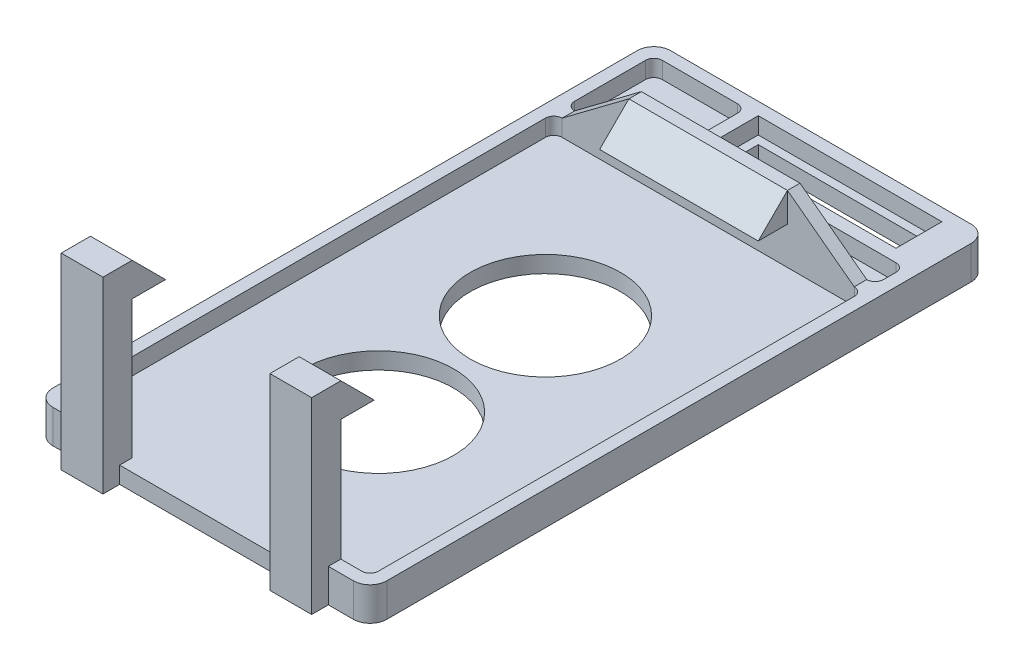
SolidWorks part; units mm, degrees
note: The reader was unsure of these and kept them because the rebuilt part matched: shared geometry of "PCB holder<52>", "PCB holder<55>", "PCB holder<57>", "PCB holder<58>", "Sketch12<3>".
ref_plane "Front Plane" through (0, 0, 0) normal (0, 0, 1) x (1, 0, 0)
ref_plane "Top Plane" through (0, 0, 0) normal (0, 1, 0) x (1, 0, 0)
ref_plane "Right Plane" through (0, 0, 0) normal (1, 0, 0) x (0, 0, -1)
sketch "PCB holder" plane through (0, 0, 0) normal (0, 1, 0) x (1, 0, 0)
  line L0 (8.75, 14.75) -> (8.75, 21.5)
  line L1 (9, 21.5) -> (-9, 21.5)
  line L2 (10, 20.5) -> (10, -14.5)
  line L3 (9, -15.5) -> (-9, -15.5)
  line L4 (-10, 20.5) -> (-10, -14.5)
  line L5 (-8.75, 14.75) -> (-8.75, 21.5)
  line L7 (8.75, 14.75) -> (-8.75, 14.75)
  line L8 (9.25, 14.25) -> (9.25, -14.25)
  line L9 (8.75, -14.75) -> (-8.75, -14.75)
  line L10 (-9.25, 14.25) -> (-9.25, -14.25)
  line L11 (-8.75, 15.5) -> (8.75, 15.5)
  line L12 (-8.75, 15.5) -> (-8.75, 14.75)
  line L13 (-4.75, 21.5) -> (4.75, 21.5)
  line L14 (-8.75, 14.75) -> (8.75, 14.75)
  line L15 (8.75, 15.5) -> (8.75, 14.75)
  line L17 (-7.5, -14.75) -> (-5, -14.75)
  line L18 (-8.75, 14.75) -> (8.75, 14.75)
  line L20 (-8.75, 21.5) -> (8.75, 21.5)
  line L22 (-7.5, -14.75) -> (-7.5, -16.5)
  line L23 (-7.5, -16.5) -> (-5, -16.5)
  line L24 (-5, -14.75) -> (-5, -16.5)
  line L25 (5, -16.5) -> (7.5, -16.5)
  line L26 (5, -16.5) -> (5, -14.75)
  line L27 (5, -14.75) -> (7.5, -14.75)
  line L28 (7.5, -16.5) -> (7.5, -14.75)
  arc A0 (-9.25, 14.25) -> (-8.75, 14.75) centre (-8.75, 14.25) cw
  arc A1 (9.25, 14.25) -> (8.75, 14.75) centre (8.75, 14.25) ccw
  arc A2 (8.75, -14.75) -> (9.25, -14.25) centre (8.75, -14.25) ccw
  arc A3 (-9.25, -14.25) -> (-8.75, -14.75) centre (-8.75, -14.25) ccw
  arc A4 (-9, 21.5) -> (-10, 20.5) centre (-9, 20.5) ccw
  arc A5 (9, 21.5) -> (10, 20.5) centre (9, 20.5) cw
  arc A6 (-10, -14.5) -> (-9, -15.5) centre (-9, -14.5) ccw
  arc A7 (10, -14.5) -> (9, -15.5) centre (9, -14.5) cw
  circle A12 centre (0, 5) radius 4.5
  circle A13 centre (0, -5) radius 4.5
  point P0 (0, 0)
  point P1 (0, 0)
  point P7 (0, 0)
  line B0 (-8.5, 14.5) -> (8.5, 14.5) construction
  line B1 (-9, 14) -> (-9, -14) construction
  line B2 (-8.5, -14.5) -> (8.5, -14.5) construction
  line B3 (9, 14) -> (9, -14) construction
  arc B4 (-9, 14) -> (-8.5, 14.5) centre (-8.5, 14) cw construction
  arc B5 (9, 14) -> (8.5, 14.5) centre (8.5, 14) ccw construction
  arc B6 (8.5, -14.5) -> (9, -14) centre (8.5, -14) ccw construction
  arc B7 (-9, -14) -> (-8.5, -14.5) centre (-8.5, -14) ccw construction
sketch_block_instance "Block2-1"
sketch_block "Block2"
extrude "Boss-Extrude1" add sketch "PCB holder" along normal blind 1 contours L10 A3 L9 A2 L8 A1 L7 A0 A13 A12 | L2 A7 L3 A6 L4 A4 L1 A5
extrude "Boss-Extrude2" add sketch "PCB holder<52>" along normal blind 1 contours L10 A3 L9 A2 L8 A1 L7 A0 A13 A12
sketch "PCB holder<52>" plane through (0, 0, 0) normal (0, 1, 0) x (1, 0, 0) same geometry as "PCB holder"
extrude "Boss-Extrude3" add sketch "PCB holder<55>" along normal blind 2 contours A7 L2 A5 L1 L0 A1 L8 A2 L9 L28 L3 | L7 L0 L1 L5 | L4 A6 L3 L22 L9 A3 L10 A0 L5 L1 A4
sketch "PCB holder<55>" plane through (0, 0, 0) normal (0, 1, 0) x (1, 0, 0) same geometry as "PCB holder"
extrude "Boss-Extrude7" add sketch "PCB holder<57>" along normal blind 5 contours L11 L5 L7 L0
sketch "PCB holder<57>" plane through (0, 0, 0) normal (0, 1, 0) x (1, 0, 0) same geometry as "PCB holder"
sketch "Sketch6" plane through (0, 0, -14.75) normal (0, 0, 1) x (1, 0, 0)
  line L1 (-4.75, 5) -> (4.75, 5)
  line L2 (-4.75, 5) -> (-4.75, 3.25)
  line L3 (-4.75, 3.25) -> (4.75, 3.25)
  line L4 (4.75, 5) -> (4.75, 3.25)
extrude "Boss-Extrude9" add sketch "Sketch6" along normal blind 1.75
sketch "Sketch7" plane through (4.75, 0, 0) normal (1, 0, 0) x (0, 0, -1)
  line L0 (13, 3.25) -> (14.75, 5)
  line L1 (14.75, 5) -> (13, 5)
  line L2 (13, 5) -> (13, 3.25)
sketch "Sketch8" plane through (0, 0, -14.75) normal (0, 0, 1) x (1, 0, 0)
  line L0 (4.75, 5) -> (8.75, 2)
  line L1 (8.75, 2) -> (8.75, 5)
  line L2 (8.75, 5) -> (4.75, 5)
  line L3 (-4.75, 5) -> (-8.75, 2)
  line L4 (-8.75, 2) -> (-8.75, 5)
  line L5 (-8.75, 5) -> (-4.75, 5)
extrude "Cut-Extrude7" cut sketch "Sketch8" against normal blind 0.75
extrude "Boss-Extrude10" add sketch "PCB holder<58>" along normal blind 11.25 contours L24 L3 L22 L23 | L24 L9 L22 L3 | L25 L28 L3 L26 | L3 L28 L9 L26
sketch "PCB holder<58>" plane through (0, 0, 0) normal (0, 1, 0) x (1, 0, 0) same geometry as "PCB holder"
sketch "Sketch10" plane through (0, 0, 14.75) normal (0, 0, -1) x (-1, 0, 0)
  line L0 (-5, 11.25) -> (-5, 1) construction
  line L1 (-7.5, 11.25) -> (-5, 11.25)
  line L2 (-7.5, 11.25) -> (-7.5, 9.25)
  line L3 (-7.5, 9.25) -> (-5, 9.25)
  line L4 (-5, 11.25) -> (-5, 9.25)
  line L5 (7.5, 11.25) -> (7.5, 2) construction
  line L6 (5, 11.25) -> (7.5, 11.25)
  line L7 (5, 11.25) -> (5, 9.25)
  line L8 (5, 9.25) -> (7.5, 9.25)
  line L9 (7.5, 11.25) -> (7.5, 9.25)
extrude "Boss-Extrude11" add sketch "Sketch10" along normal blind 2
sketch "Sketch11" plane through (7.5, 0, 0) normal (1, 0, 0) x (0, 0, -1)
  line L0 (-14.75, 11.25) -> (-12.75, 9.25)
  line L1 (-16.5, 11.25) -> (-12.75, 11.25) construction
  line L2 (-12.75, 9.25) -> (-12.75, 11.25)
  line L3 (-12.75, 11.25) -> (-12.75, 9.25) construction
  line L4 (-12.75, 11.25) -> (-14.75, 11.25)
extrude "Cut-Extrude8" cut sketch "Sketch11" against normal blind 15
extrude "Cut-Extrude12" cut sketch "Sketch7" against normal blind 9.5 contours L0 L1 L2
sketch "Sketch12" plane through (0, 2, 0) normal (0, 1, 0) x (1, 0, 0)
  line L0 (9.25, 16) -> (9.25, 16.75)
  line L1 (-4.25, 20.75) -> (-8.75, 20.75)
  line L2 (-9.25, 20.25) -> (-9.25, 16)
  line L3 (-8.75, 15.5) -> (8.75, 15.5)
  line L5 (-3, 20.75) -> (8, 20.75) construction
  line L6 (-3, 20.75) -> (-3, 18) construction
  line L7 (-3, 18) -> (8, 18) construction
  line L8 (8, 20.75) -> (8, 18) construction
  line L9 (-3, 20.75) -> (8, 20.75)
  line L10 (-3.75, 20.25) -> (-3.75, 17.75)
  line L11 (-3.25, 17.25) -> (8.75, 17.25)
  line L12 (-3, 20.75) -> (-3, 18)
  line L13 (-3, 18) -> (8, 18)
  line L14 (8, 20.75) -> (8, 18)
  line L15 (-2.5, 20.25) -> (7.5, 20.25)
  line L16 (-2.5, 20.25) -> (-2.5, 18.5)
  line L17 (-2.5, 18.5) -> (7.5, 18.5)
  line L18 (7.5, 20.25) -> (7.5, 18.5)
  arc A0 (8.75, 15.5) -> (9.25, 16) centre (8.75, 16) ccw
  arc A1 (9.25, 16.75) -> (8.75, 17.25) centre (8.75, 16.75) ccw
  arc A2 (-9.25, 20.25) -> (-8.75, 20.75) centre (-8.75, 20.25) cw
  arc A3 (-8.75, 15.5) -> (-9.25, 16) centre (-8.75, 16) cw
  arc A4 (-3.75, 17.75) -> (-3.25, 17.25) centre (-3.25, 17.75) ccw
  arc A5 (-3.75, 20.25) -> (-4.25, 20.75) centre (-4.25, 20.25) ccw
extrude "Cut-Extrude15" cut sketch "Sketch12" against normal blind 1
extrude "Cut-Extrude16" cut sketch "Sketch12<3>" against normal blind 2 contours L18 L15 L16 L17
sketch "Sketch12<3>" plane through (0, 2, 0) normal (0, 1, 0) x (1, 0, 0) same geometry as "Sketch12"
